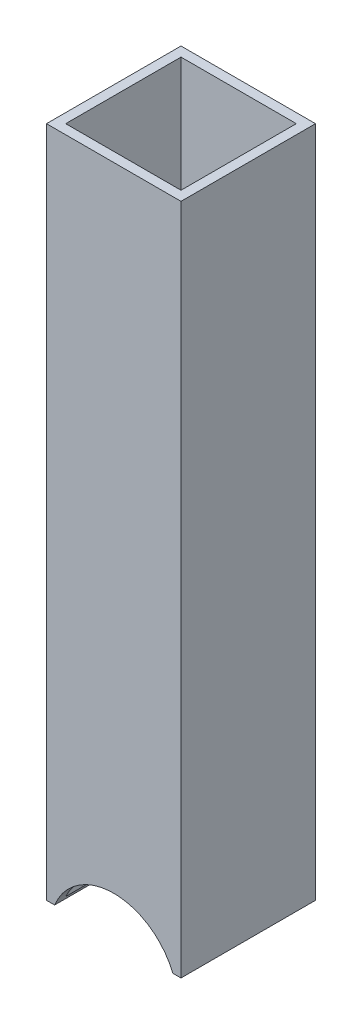
SolidWorks part; units mm, degrees
material "6061-T6 (SS)"
ref_plane "Front Plane" through (0, 0, 0) normal (0, 0, 1) x (1, 0, 0)
ref_plane "Top Plane" through (0, 0, 0) normal (0, 1, 0) x (1, 0, 0)
ref_plane "Right Plane" through (0, 0, 0) normal (1, 0, 0) x (0, 0, -1)
sketch "Sketch1" plane through (0, 0, 0) normal (0, 1, 0) x (1, 0, 0)
  line L1 (-22.225, -22.225) -> (22.225, -22.225)
  line L2 (-22.225, -22.225) -> (-22.225, 22.225)
  line L3 (-22.225, 22.225) -> (22.225, 22.225)
  line L4 (22.225, -22.225) -> (22.225, 22.225)
  line L5 (-22.225, -22.225) -> (22.225, 22.225) construction
  line L6 (-22.225, 22.225) -> (22.225, -22.225) construction
  line L7 (-19.05, -19.05) -> (19.05, -19.05)
  line L8 (-19.05, -19.05) -> (-19.05, 19.05)
  line L9 (-19.05, 19.05) -> (19.05, 19.05)
  line L10 (19.05, -19.05) -> (19.05, 19.05)
  line L11 (-19.05, -19.05) -> (19.05, 19.05) construction
  line L12 (-19.05, 19.05) -> (19.05, -19.05) construction
  point P0 (0, 0)
  point P6 (0, 0)
  dimension "D1" = 44.45
  dimension "D2" = 3.175
extrude "Boss-Extrude1" add sketch "Sketch1" along normal blind 95.25 and the other way blind 95.25
sketch "Sketch2" plane through (0, -95.25, 0) normal (0, -1, 0) x (1, 0, 0)
  line L0 (19.05, 19.05) -> (19.05, -19.05) construction
  line L1 (19.05, -19.05) -> (-19.05, -19.05) construction
  line L2 (-19.05, -19.05) -> (-19.05, 19.05) construction
  line L3 (-19.05, 19.05) -> (19.05, 19.05) construction
  line L4 (22.225, -22.225) -> (22.225, 22.225)
  line L5 (22.225, 22.225) -> (-22.225, 22.225)
  line L6 (-22.225, 22.225) -> (-22.225, -22.225)
  line L7 (-22.225, -22.225) -> (22.225, -22.225)
  line L8 (22.225, -22.225) -> (22.225, 22.225)
  line L9 (22.225, 22.225) -> (-22.225, 22.225)
  line L10 (-22.225, 22.225) -> (-22.225, -22.225)
  line L11 (-22.225, -22.225) -> (22.225, -22.225)
  line L12 (19.05, 19.05) -> (19.05, -19.05)
  line L13 (19.05, -19.05) -> (-19.05, -19.05)
  line L14 (-19.05, -19.05) -> (-19.05, 19.05)
  line L15 (-19.05, 19.05) -> (19.05, 19.05)
  dimension "D1" = 0
extrude "Boss-Extrude2" add sketch "Sketch2" along normal blind 31.75
sketch "Sketch3" plane through (0, 0, 22.225) normal (0, 0, 1) x (1, 0, 0)
  line L0 (-22.225, -88.9) -> (22.225, -88.9) construction
  line L1 (-22.225, -127) -> (-22.225, 95.25) construction
  line L2 (22.225, -127) -> (22.225, 95.25) construction
  line L3 (22.225, -127) -> (-22.225, -127) construction
  circle A0 centre (0, -134.9375) radius 21.082
  dimension "D1" = 42.164
  dimension "D2" = 38.1
  dimension "D3" = 46.0375
extrude "Cut-Extrude1" cut sketch "Sketch3" against normal through all
